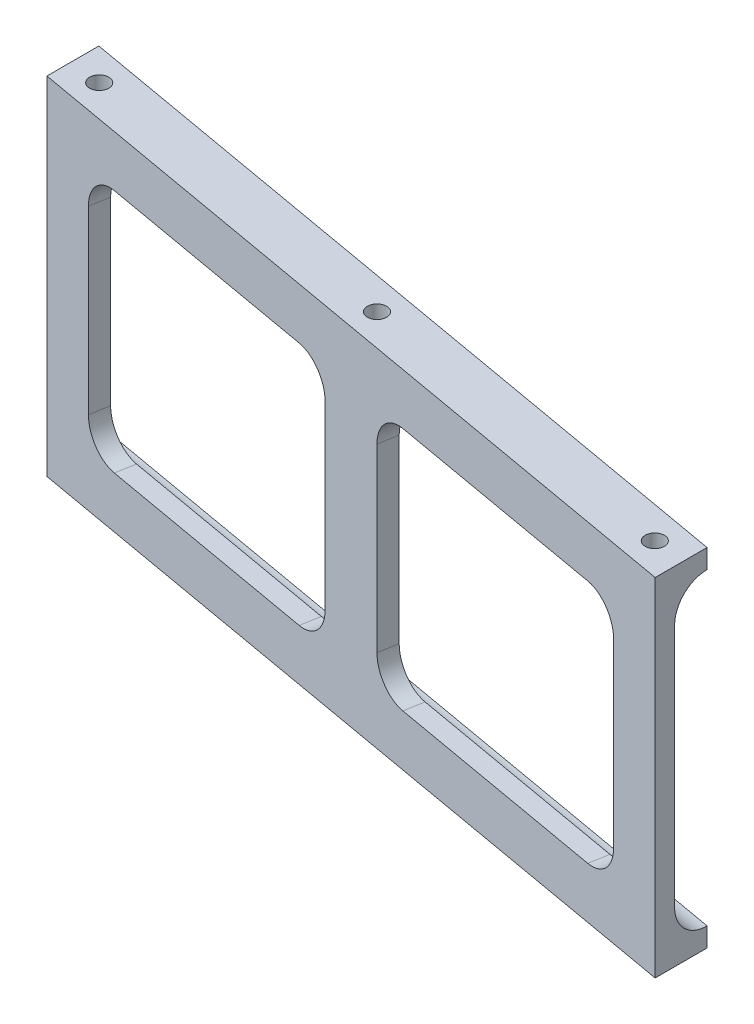
SolidWorks part; units mm, degrees
ref_plane "Front Plane" through (0, 0, 0) normal (0, 0, 1) x (1, 0, 0)
ref_plane "Top Plane" through (0, 0, 0) normal (0, 1, 0) x (1, 0, 0)
ref_plane "Right Plane" through (0, 0, 0) normal (1, 0, 0) x (0, 0, -1)
sketch "Sketch1" plane through (0, -6.8481, 0) normal (0, 1, 0) x (1, 0, 0)
  line L0 (-57.75, -74.4929) -> (57.75, -94.8587)
  line L1 (57.75, -94.8587) -> (57.75, -91.8124)
  line L2 (57.75, -94.8587) -> (57.75, -62.2403) construction
  line L3 (57.75, -91.8124) -> (-57.75, -71.4466)
  line L4 (-57.75, -32.7635) -> (-57.75, -74.4929) construction
  line L5 (-57.75, -71.4466) -> (-57.75, -74.4929)
  dimension "D1" = 3
extrude "Main bracket extrude" add sketch "Sketch1" along normal up to surface (54.25 mm away)
sketch "Sketch2" plane through (0, 47.4019, 0) normal (0, 1, 0) x (1, 0, 0)
  line L0 (-57.75, -74.4929) -> (-57.75, -66.3695)
  line L1 (-57.75, -66.3695) -> (57.75, -86.7353)
  line L2 (57.75, -86.7353) -> (57.75, -94.8587)
  line L3 (57.75, -94.8587) -> (-57.75, -74.4929)
  line L4 (57.75, -94.8587) -> (57.75, -91.8124) construction
  point P3 (59.008, -86.8711)
  dimension "D1" = 8
extrude "Top screwhole extension" add sketch "Sketch2" against normal blind 3
sketch "Sketch3" plane through (0, -6.8481, 0) normal (0, -1, 0) x (1, 0, 0)
  line L4 (-57.75, 74.4929) -> (-57.75, 66.3695)
  line L5 (57.75, 94.8587) -> (-57.75, 74.4929)
  line L6 (57.75, 86.7353) -> (57.75, 94.8587)
  line L7 (-57.75, 66.3695) -> (57.75, 86.7353)
  line L8 (-57.75, 74.4929) -> (-57.75, 66.3695)
  line L9 (57.75, 94.8587) -> (-57.75, 74.4929)
  line L10 (57.75, 86.7353) -> (57.75, 94.8587)
  line L11 (-57.75, 66.3695) -> (57.75, 86.7353)
  dimension "D1" = 0
extrude "Bottom screwhole extension" add sketch "Sketch3" against normal blind 3
fillet "Screwhole extension fillets 5mm" radius 5 2 edges at (0, 44.4019, 81.6295) (0, -3.8481, 81.6295)
sketch "Sketch4" plane through (0, 47.4019, 0) normal (0, 1, 0) x (1, 0, 0)
  line L0 (-57.75, -70.4312) -> (57.75, -90.797) construction
  line L1 (-57.75, -66.3695) -> (-57.75, -74.4929) construction
  line L2 (57.75, -94.8587) -> (57.75, -86.7353) construction
  circle A0 centre (-52.75, -71.3129) radius 1.5
  circle A1 centre (0, -80.6141) radius 1.5
  circle A2 centre (52.75, -89.9153) radius 1.5
  point P12 (-49.0213, -71.9703)
  point P13 (0, -80.6141)
  point P14 (49.618, -89.3631)
  dimension "D1" = 3
  dimension "D2" = 5
  dimension "D3" = 5
extrude "Top screwholes" cut sketch "Sketch4" against normal blind 8
sketch "Sketch5" plane through (0, -6.8481, 0) normal (0, -1, 0) x (1, 0, 0)
  circle A0 centre (52.75, 89.9153) radius 1.5 construction
  circle A1 centre (0, 80.6141) radius 1.5 construction
  circle A2 centre (-52.75, 71.3129) radius 1.5 construction
  circle A3 centre (52.75, 89.9153) radius 1.5
  circle A4 centre (0, 80.6141) radius 1.5
  circle A5 centre (-52.75, 71.3129) radius 1.5
extrude "Bottom screwholes" cut sketch "Sketch5" against normal blind 8
sketch "Sketch6" plane through (-14.4804, 0, 82.1225) normal (-0.1736, 0, 0.9848) x (0.9848, 0, 0.1736)
  line L0 (-43.9371, 47.4019) -> (73.3447, 47.4019) construction
  line L1 (-30.9371, 39.4019) -> (4.7038, 39.4019)
  line L2 (-35.9371, 34.4019) -> (-35.9371, 6.1519)
  line L3 (-30.9371, 1.1519) -> (4.7038, 1.1519)
  line L4 (9.7038, 34.4019) -> (9.7038, 6.1519)
  line L5 (24.7038, 39.4019) -> (60.3447, 39.4019)
  line L6 (19.7038, 34.4019) -> (19.7038, 6.1519)
  line L7 (24.7038, 1.1519) -> (60.3447, 1.1519)
  line L8 (65.3447, 34.4019) -> (65.3447, 6.1519)
  line L9 (-43.9371, -6.8481) -> (73.3447, -6.8481) construction
  line L10 (-43.9371, 47.4019) -> (-43.9371, -6.8481) construction
  line L11 (73.3447, 47.4019) -> (73.3447, -6.8481) construction
  arc A0 (60.3447, 39.4019) -> (65.3447, 34.4019) centre (60.3447, 34.4019) cw
  arc A1 (60.3447, 1.1519) -> (65.3447, 6.1519) centre (60.3447, 6.1519) ccw
  arc A2 (19.7038, 6.1519) -> (24.7038, 1.1519) centre (24.7038, 6.1519) ccw
  arc A3 (24.7038, 39.4019) -> (19.7038, 34.4019) centre (24.7038, 34.4019) ccw
  arc A4 (4.7038, 39.4019) -> (9.7038, 34.4019) centre (4.7038, 34.4019) cw
  arc A5 (4.7038, 1.1519) -> (9.7038, 6.1519) centre (4.7038, 6.1519) ccw
  arc A6 (-35.9371, 6.1519) -> (-30.9371, 1.1519) centre (-30.9371, 6.1519) ccw
  arc A7 (-30.9371, 39.4019) -> (-35.9371, 34.4019) centre (-30.9371, 34.4019) ccw
  dimension "D8" = 5
  dimension "D1" = 8
  dimension "D2" = 8
  dimension "D3" = 8
  dimension "D4" = 8
  dimension "D5" = 8
  dimension "D6" = 8
  dimension "D7" = 10
extrude "Weight reduction" cut sketch "Sketch6" against normal through all both and the other way through all
